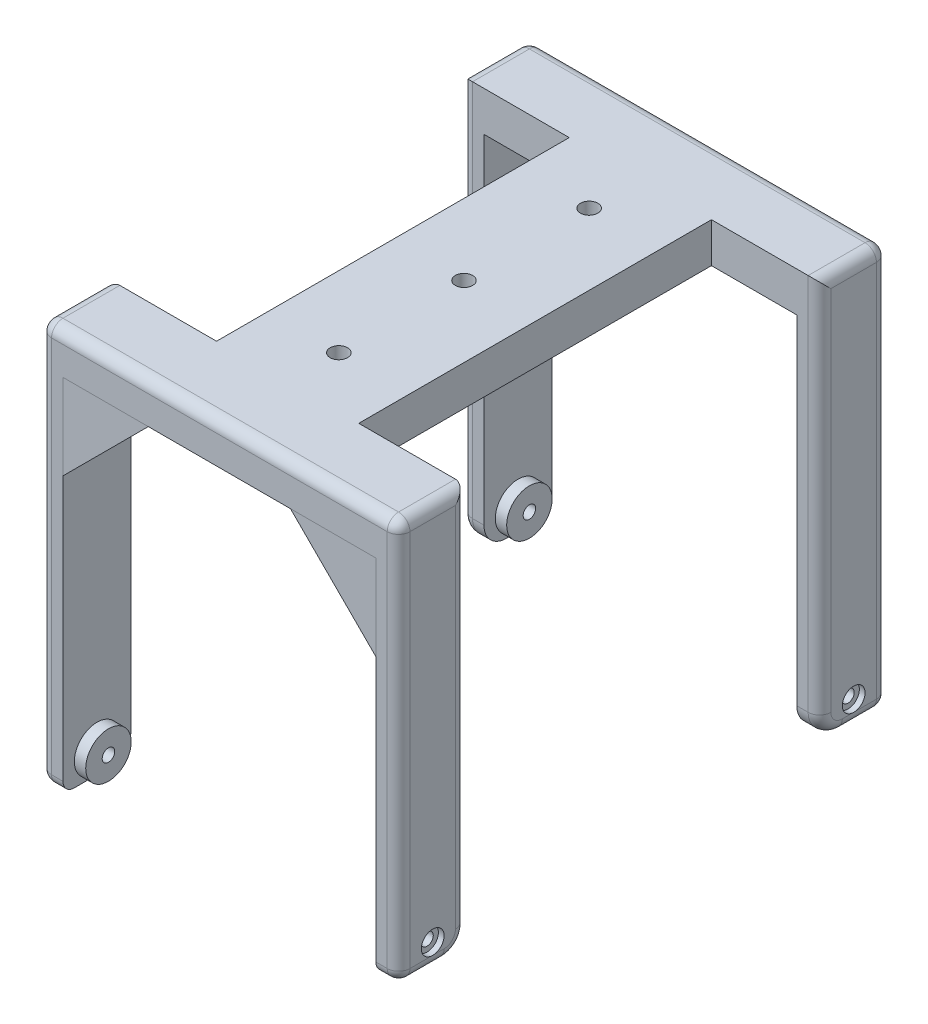
SolidWorks part; units mm, degrees
ref_plane "前视基准面" through (0, 0, 0) normal (0, 0, 1) x (1, 0, 0)
ref_plane "上视基准面" through (0, 0, 0) normal (0, 1, 0) x (1, 0, 0)
ref_plane "右视基准面" through (0, 0, 0) normal (1, 0, 0) x (0, 0, -1)
sketch "草图1" plane through (0, 0, 0) normal (0, 1, 0) x (1, 0, 0)
  line L1 (-31.5, 6) -> (31.5, 6)
  line L2 (-31.5, 6) -> (-31.5, -6)
  line L3 (-31.5, -6) -> (31.5, -6)
  line L4 (31.5, 6) -> (31.5, -6)
  line L5 (-31.5, 6) -> (31.5, -6) construction
  line L6 (-31.5, -6) -> (31.5, 6) construction
  point P0 (0, 0)
  dimension "D1" = 12
  dimension "D2" = 63
extrude "凸台-拉伸1" add sketch "草图1" along normal blind 70.5
sketch "草图2" plane through (0, 0, 6) normal (0, 0, 1) x (1, 0, 0)
  line L0 (-31.5, 0) -> (31.5, 0) construction
  line L1 (-27.5, 63.5) -> (27.5, 63.5)
  line L2 (-27.5, 63.5) -> (-27.5, 0)
  line L3 (-27.5, 0) -> (27.5, 0)
  line L4 (27.5, 63.5) -> (27.5, 0)
  line L5 (-31.5, 70.5) -> (-31.5, 0) construction
  line L6 (31.5, 70.5) -> (31.5, 0) construction
  line L7 (-31.5, 70.5) -> (31.5, 70.5) construction
  dimension "D1" = 4
  dimension "D2" = 4
  dimension "D3" = 7
extrude "切除-拉伸1" cut sketch "草图2" against normal through all
sketch "草图4" plane through (0, 0, -6) normal (0, 0, -1) x (-1, 0, 0)
  line L0 (-31.5, 70.5) -> (31.5, 70.5) construction
  line L1 (-12.5, 70.5) -> (12.5, 70.5)
  line L2 (-12.5, 70.5) -> (-12.5, 63.5)
  line L3 (-12.5, 63.5) -> (12.5, 63.5)
  line L4 (12.5, 70.5) -> (12.5, 63.5)
  line L5 (-27.5, 63.5) -> (27.5, 63.5) construction
  line L6 (0, 0) -> (0, 63.5) construction
  dimension "D1" = 25
extrude "凸台-拉伸2" add sketch "草图4" along normal blind 62
sketch "草图5" plane through (0, 0, -68) normal (0, 0, -1) x (-1, 0, 0)
  line L1 (12.5, 63.5) -> (27.5, 63.5) construction
  line L2 (27.5, 63.5) -> (27.5, 0) construction
  line L3 (27.5, 0) -> (31.5, 0) construction
  line L4 (31.5, 0) -> (31.5, 70.5) construction
  line L5 (31.5, 70.5) -> (12.5, 70.5) construction
  line L7 (-12.5, 63.5) -> (12.5, 63.5) construction
  line L9 (12.5, 70.5) -> (-12.5, 70.5) construction
  line L11 (-12.5, 70.5) -> (-31.5, 70.5) construction
  line L12 (-31.5, 70.5) -> (-31.5, 0) construction
  line L13 (-31.5, 0) -> (-27.5, 0) construction
  line L14 (-27.5, 0) -> (-27.5, 63.5) construction
  line L15 (-27.5, 63.5) -> (-12.5, 63.5) construction
  line L17 (12.5, 63.5) -> (27.5, 63.5)
  line L18 (27.5, 63.5) -> (27.5, 0)
  line L19 (27.5, 0) -> (31.5, 0)
  line L20 (31.5, 0) -> (31.5, 70.5)
  line L21 (31.5, 70.5) -> (12.5, 70.5)
  line L23 (-12.5, 63.5) -> (12.5, 63.5)
  line L25 (12.5, 70.5) -> (-12.5, 70.5)
  line L27 (-12.5, 70.5) -> (-31.5, 70.5)
  line L28 (-31.5, 70.5) -> (-31.5, 0)
  line L29 (-31.5, 0) -> (-27.5, 0)
  line L30 (-27.5, 0) -> (-27.5, 63.5)
  line L31 (-27.5, 63.5) -> (-12.5, 63.5)
extrude "凸台-拉伸3" add sketch "草图5" along normal blind 12
sketch "草图3" plane through (31.5, 0, 0) normal (1, 0, 0) x (0, 0, -1)
  line L1 (0, 4) -> (0, 0) construction
  line L3 (80, 0) -> (68, 0) construction
  line L4 (74, 4) -> (74, 0) construction
  circle A0 centre (0, 4) radius 1.1
  circle A1 centre (74, 4) radius 1.1
  dimension "D1" = 2.2
  dimension "D2" = 4
  dimension "D3" = 4
extrude "切除-拉伸2" cut sketch "草图3" against normal through all
sketch "草图7" plane through (-27.5, 0, 0) normal (1, 0, 0) x (0, 0, -1)
  circle A0 centre (0, 4) radius 4
  circle A1 centre (74, 4) radius 4
  circle A2 centre (74, 4) radius 1.1 construction
  circle A3 centre (0, 4) radius 1.1 construction
  circle A4 centre (74, 4) radius 1.1
  circle A5 centre (0, 4) radius 1.1
  dimension "D1" = 8
extrude "凸台-拉伸4" add sketch "草图7" along normal blind 2
sketch "草图8" plane through (27.5, 0, 0) normal (-1, 0, 0) x (0, 0, 1)
  circle A0 centre (-74, 4) radius 4
  circle A1 centre (0, 4) radius 4
  circle A2 centre (0, 4) radius 1.1 construction
  circle A3 centre (-74, 4) radius 1.1 construction
  circle A4 centre (0, 4) radius 1.1
  circle A5 centre (-74, 4) radius 1.1
  dimension "D1" = 8
extrude "凸台-拉伸5" add sketch "草图8" along normal blind 2
sketch "草图13" plane through (0, 0, 6) normal (0, 0, 1) x (1, 0, 0)
  line L0 (-27.5, 63.5) -> (-27.5, 48.5)
  line L1 (-27.5, 63.5) -> (-27.5, 0) construction
  line L2 (-27.5, 48.5) -> (-12.5, 63.5)
  line L3 (27.5, 63.5) -> (-27.5, 63.5) construction
  line L4 (-12.5, 63.5) -> (-27.5, 63.5)
  line L5 (0, 79.1636) -> (0, -19.0461) construction
  line L6 (27.5, 48.5) -> (12.5, 63.5)
  line L7 (27.5, 63.5) -> (27.5, 48.5)
  line L8 (12.5, 63.5) -> (27.5, 63.5)
  dimension "D1" = 15
extrude "凸台-拉伸6" add sketch "草图13" against normal blind 4 separate body
sketch "草图14" plane through (0, 0, -80) normal (0, 0, -1) x (-1, 0, 0)
  line L0 (27.5, 63.5) -> (12.5, 63.5) construction
  line L1 (12.5, 63.5) -> (27.5, 48.5) construction
  line L2 (27.5, 48.5) -> (27.5, 63.5) construction
  line L3 (-27.5, 63.5) -> (-27.5, 48.5) construction
  line L4 (-27.5, 48.5) -> (-12.5, 63.5) construction
  line L5 (-12.5, 63.5) -> (-27.5, 63.5) construction
  line L6 (27.5, 63.5) -> (12.5, 63.5)
  line L7 (12.5, 63.5) -> (27.5, 48.5)
  line L8 (27.5, 48.5) -> (27.5, 63.5)
  line L9 (-27.5, 63.5) -> (-27.5, 48.5)
  line L10 (-27.5, 48.5) -> (-12.5, 63.5)
  line L11 (-12.5, 63.5) -> (-27.5, 63.5)
extrude "凸台-拉伸7" add sketch "草图14" against normal blind 4
sketch "草图9" plane through (0, 63.5, 0) normal (0, -1, 0) x (1, 0, 0)
  line L0 (0, -15) -> (0, -59) construction
  line L1 (-12.5, -37) -> (0, -37) construction
  line L2 (-12.5, -68) -> (-12.5, -6) construction
  line L3 (0, 0) -> (0, -15) construction
  circle A0 centre (0, -15) radius 1.1
  circle A1 centre (0, -59) radius 1.1
  circle A2 centre (0, -37) radius 1.1
  dimension "D1" = 2.2
  dimension "D2" = 44
extrude "切除-拉伸3" cut sketch "草图9" against normal through all
sketch "草图10" plane through (0, 63.5, 0) normal (0, -1, 0) x (1, 0, 0)
  circle A0 centre (0, -15) radius 4.1
  circle A1 centre (0, -59) radius 4.1
  circle A2 centre (0, -37) radius 4.1
  dimension "D1" = 8.2
extrude "切除-拉伸4" cut sketch "草图10" against normal blind 2
sketch "草图11" plane through (31.5, 0, 0) normal (1, 0, 0) x (0, 0, -1)
  circle A0 centre (0, 4) radius 2
  circle A1 centre (74, 4) radius 2
  dimension "D1" = 4
extrude "切除-拉伸5" cut sketch "草图11" against normal blind 1
sketch "草图12" plane through (-31.5, 0, 0) normal (-1, 0, 0) x (0, 0, 1)
  circle A0 centre (-74, 4) radius 2
  circle A1 centre (0, 4) radius 2
  dimension "D1" = 4
extrude "切除-拉伸6" cut sketch "草图12" against normal blind 1
sketch "草图15" plane through (0, 70.5, 0) normal (0, 1, 0) x (1, 0, 0)
  circle A0 centre (0, 59) radius 1.525
  circle A1 centre (0, 37) radius 1.525
  circle A2 centre (0, 15) radius 1.525
  dimension "D1" = 3.05
extrude "切除-拉伸7" cut sketch "草图15" against normal blind 3
fillet "圆角1" radius 4 4 edges at (29.5, 0, -68) (29.5, 0, -6) (-29.5, 0, -6) (-29.5, 0, -68)
fillet "圆角2" radius 2 4 edges at (29.5, 0, -80) (-29.5, 0, -80) (-29.5, 0, 6) (29.5, 0, 6)
fillet "圆角3" radius 2 2 edges at (0, 70.5, 6) (0, 70.5, -80)
fillet "圆角4" radius 2 28 edges at (-31.5, 37.25, -6) (-31.5, 1.1716, -4.8284) (-31.5, 0, 1) (-31.5, 0.5858, 5.4142) (-31.5, 35.25, 6) (-31.5, 69.9142, 5.4142) (-31.5, 37.25, -68) (-31.5, 1.1716, -69.1716) (-31.5, 0, -75) (-31.5, 0.5858, -79.4142) (-31.5, 35.25, -80) (-31.5, 69.9142, -79.4142) (31.5, 37.25, -68) (31.5, 1.1716, -69.1716) (31.5, 0, -75) (31.5, 0.5858, -79.4142) (31.5, 35.25, -80) (31.5, 69.9142, -79.4142) (31.5, 37.25, -6) (31.5, 1.1716, -4.8284) (31.5, 0, 1) (31.5, 0.5858, 5.4142) (31.5, 35.25, 6) (31.5, 69.9142, 5.4142) (-31.5, 70.5, -1) (-31.5, 70.5, -73) (31.5, 70.5, -73) (31.5, 70.5, -1)
